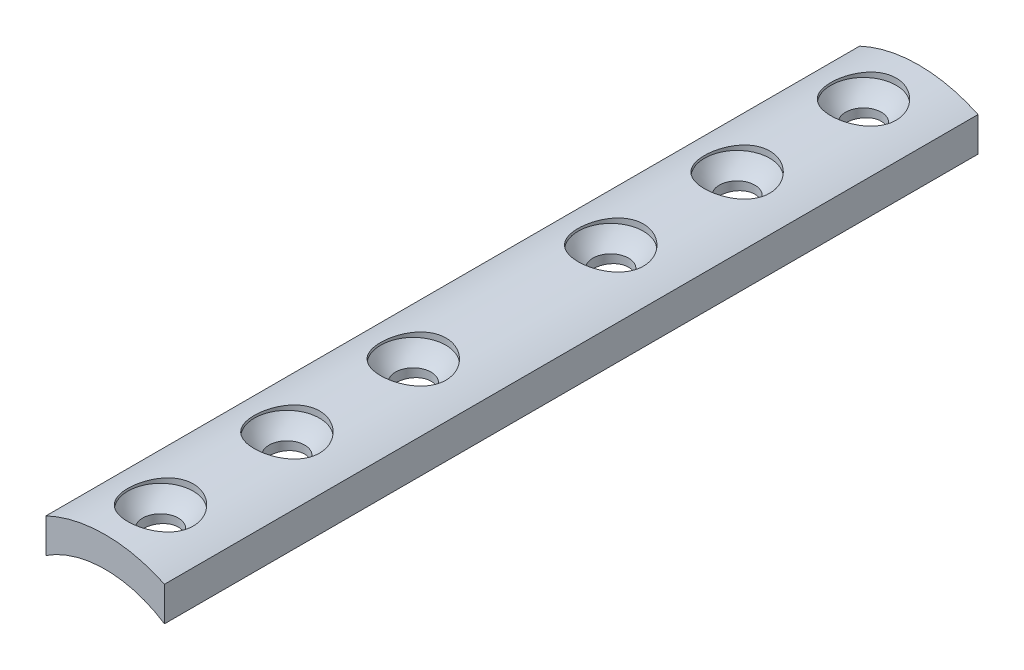
SolidWorks part; units mm, degrees
material "Ti-3Al-8V-6Cr-4Mo-4Zr (SS)"
ref_plane "Front Plane" through (0, 0, 0) normal (0, 0, 1) x (1, 0, 0)
ref_plane "Top Plane" through (0, 0, 0) normal (0, 1, 0) x (1, 0, 0)
ref_plane "Right Plane" through (0, 0, 0) normal (1, 0, 0) x (0, 0, -1)
sketch "Sketch1" plane through (0, 0, 0) normal (0, 0, 1) x (1, 0, 0)
  line L0 (0, -11.4647) -> (0, 6.0353) construction
  line L1 (-7.5, 4.3467) -> (-7.5, 0)
  line L2 (7.5, 4.3467) -> (7.5, 0)
  line L4 (-7.5, 0) -> (7.5, 0) construction
  arc A0 (-7.5, 0) -> (7.5, 0) centre (0, -11.4647) cw
  arc A1 (-7.5, 4.3467) -> (7.5, 4.3467) centre (0, -11.4647) cw
  arc A2 (-16.9478, -15.8262) -> (16.9428, -15.8455) centre (0, -11.4647) cw construction
  arc A3 (-13.2677, -14.8791) -> (13.2638, -14.8942) centre (0, -11.4647) cw construction
  dimension "D1" = 3.8
  dimension "D3" = 15
  dimension "D2" = 13.7
extrude "Boss-Extrude1" add sketch "Sketch1" against normal blind 103
sketch "Sketch2" plane through (0, 0, 0) normal (0, 1, 0) x (1, 0, 0)
  line L0 (7.5, 103) -> (-7.5, 103) construction
  line L1 (-7.5, 0) -> (7.5, 0) construction
  circle A0 centre (0, 96) radius 4.05
  circle A1 centre (0, 80) radius 4.05
  circle A2 centre (0, 64) radius 4.05
  circle A3 centre (0, 39) radius 4.05
  circle A4 centre (0, 23) radius 4.05
  circle A5 centre (0, 7) radius 4.05
  circle A6 centre (0, 96) radius 2.25
  circle A7 centre (0, 80) radius 2.25
  circle A8 centre (0, 64) radius 2.25
  circle A9 centre (0, 39) radius 2.25
  circle A10 centre (0, 23) radius 2.25
  circle A11 centre (0, 7) radius 2.25
  point P20 (0, 0)
  dimension "D8" = 8.1
  dimension "D9" = 4.5
  dimension "D1" = 7
  dimension "D2" = 7
  dimension "D3" = 25
  dimension "D4" = 16
  dimension "D5" = 16
  dimension "D6" = 16
  dimension "D7" = 16
extrude "Cut-Extrude2" cut sketch "Sketch2" against normal blind 11 from offset 6.04 contours A9 | A8 | A10 | A11 | A7 | A6 region at (0, 0, -96) region at (0, 0, -80) region at (0, 0, -64) region at (0, 0, -39) region at (0, 0, -23) region at (0, 0, -7)
sketch "Sketch3" plane through (0, 0, 0) normal (1, 0, 0) x (0, 0, -1)
  line L0 (7, 0) -> (7, 10.3493) construction
  line L1 (103, 0) -> (0, 0) construction
  line L2 (7, 6.0353) -> (2.8627, 6.0353)
  line L3 (23, 5.89) -> (23, 0) construction
  line L4 (2.8627, 6.0353) -> (2.8627, 5.2353)
  line L5 (39, 5.89) -> (39, 0) construction
  line L6 (4.75, 6.0353) -> (4.75, 2.2353) construction
  line L7 (4.75, 3.2353) -> (7, 3.2353)
  line L8 (7, 3.2353) -> (7, 6.0353)
  line L9 (64, 5.89) -> (64, 0) construction
  line L10 (80, 5.89) -> (80, 0) construction
  line L11 (96, 5.89) -> (96, 0) construction
  line L12 (23, 6.0353) -> (18.8627, 6.0353)
  line L13 (20.75, 3.2353) -> (23, 3.2353)
  line L14 (18.8627, 6.0353) -> (18.8627, 5.2353)
  line L15 (23, 3.2353) -> (23, 6.0353)
  line L16 (39, 6.0353) -> (34.8627, 6.0353)
  line L17 (36.75, 3.2353) -> (39, 3.2353)
  line L18 (34.8627, 6.0353) -> (34.8627, 5.2353)
  line L19 (39, 3.2353) -> (39, 6.0353)
  line L20 (64, 6.0353) -> (59.8627, 6.0353)
  line L21 (61.75, 3.2353) -> (64, 3.2353)
  line L22 (59.8627, 6.0353) -> (59.8627, 5.2353)
  line L23 (64, 3.2353) -> (64, 6.0353)
  line L24 (80, 6.0353) -> (75.8627, 6.0353)
  line L25 (77.75, 3.2353) -> (80, 3.2353)
  line L26 (75.8627, 6.0353) -> (75.8627, 5.2353)
  line L27 (80, 3.2353) -> (80, 6.0353)
  line L28 (96, 6.0353) -> (91.8627, 6.0353)
  line L29 (93.75, 3.2353) -> (96, 3.2353)
  line L30 (91.8627, 6.0353) -> (91.8627, 5.2353)
  line L31 (96, 3.2353) -> (96, 6.0353)
  arc A0 (2.8627, 5.2353) -> (4.75, 3.2353) centre (8.7982, 8.9459) ccw
  arc A1 (18.8627, 5.2353) -> (20.75, 3.2353) centre (24.7982, 8.9459) ccw
  arc A2 (34.8627, 5.2353) -> (36.75, 3.2353) centre (40.7982, 8.9459) ccw
  arc A3 (59.8627, 5.2353) -> (61.75, 3.2353) centre (65.7982, 8.9459) ccw
  arc A4 (75.8627, 5.2353) -> (77.75, 3.2353) centre (81.7982, 8.9459) ccw
  arc A5 (91.8627, 5.2353) -> (93.75, 3.2353) centre (97.7982, 8.9459) ccw
  spline S0 degree 2 poles (25.25, 6.0353) (23, 5.746) (20.75, 6.0353) knots 0 0 0 1 1 1 weights 0.01525 0.0175 0.01975 construction
  spline S1 degree 2 poles (41.25, 6.0353) (39, 5.746) (36.75, 6.0353) knots 0 0 0 1 1 1 weights 0.01525 0.0175 0.01975 construction
  spline S2 degree 2 poles (66.25, 6.0353) (64, 5.746) (61.75, 6.0353) knots 0 0 0 1 1 1 weights 0.01525 0.0175 0.01975 construction
  spline S3 degree 2 poles (82.25, 6.0353) (80, 5.746) (77.75, 6.0353) knots 0 0 0 1 1 1 weights 0.01525 0.0175 0.01975 construction
  spline S4 degree 2 poles (98.25, 6.0353) (96, 5.746) (93.75, 6.0353) knots 0 0 0 1 1 1 weights 0.01525 0.0175 0.01975 construction
  point P8 (7, 6.0353)
  dimension "D2" = 7
  dimension "D1" = 2.25
  dimension "D3" = 2
  dimension "D4" = 2.8
  dimension "D5" = 4.1373
  dimension "D6" = 3.2353
  dimension "D7" = 16
  dimension "D8" = 16
  dimension "D9" = 25
  dimension "D10" = 16
  dimension "D11" = 16
revolve "Cut-Revolve1" cut sketch "Sketch3" angle 360 about L0 region at (0, 4.7634, -5.1751)
revolve "Cut-Revolve2" cut sketch "Sketch3<3>" angle 360 about L3 region at (0, 4.7634, -21.1751)
sketch "Sketch3<3>" plane through (0, 0, 0) normal (1, 0, 0) x (0, 0, -1) same geometry as "Sketch3"
revolve "Cut-Revolve3" cut sketch "Sketch3<4>" angle 360 about L5 region at (0, 4.7634, -37.1751)
sketch "Sketch3<4>" plane through (0, 0, 0) normal (1, 0, 0) x (0, 0, -1) same geometry as "Sketch3"
revolve "Cut-Revolve4" cut sketch "Sketch3<5>" angle 360 about L9 region at (0, 4.7634, -62.1751)
sketch "Sketch3<5>" plane through (0, 0, 0) normal (1, 0, 0) x (0, 0, -1) same geometry as "Sketch3"
revolve "Cut-Revolve5" cut sketch "Sketch3<6>" angle 360 about L10 region at (0, 4.7634, -78.1751)
sketch "Sketch3<6>" plane through (0, 0, 0) normal (1, 0, 0) x (0, 0, -1) same geometry as "Sketch3"
revolve "Cut-Revolve6" cut sketch "Sketch3<7>" angle 360 about L11 region at (0, 4.7634, -94.1751)
sketch "Sketch3<7>" plane through (0, 0, 0) normal (1, 0, 0) x (0, 0, -1) same geometry as "Sketch3"
